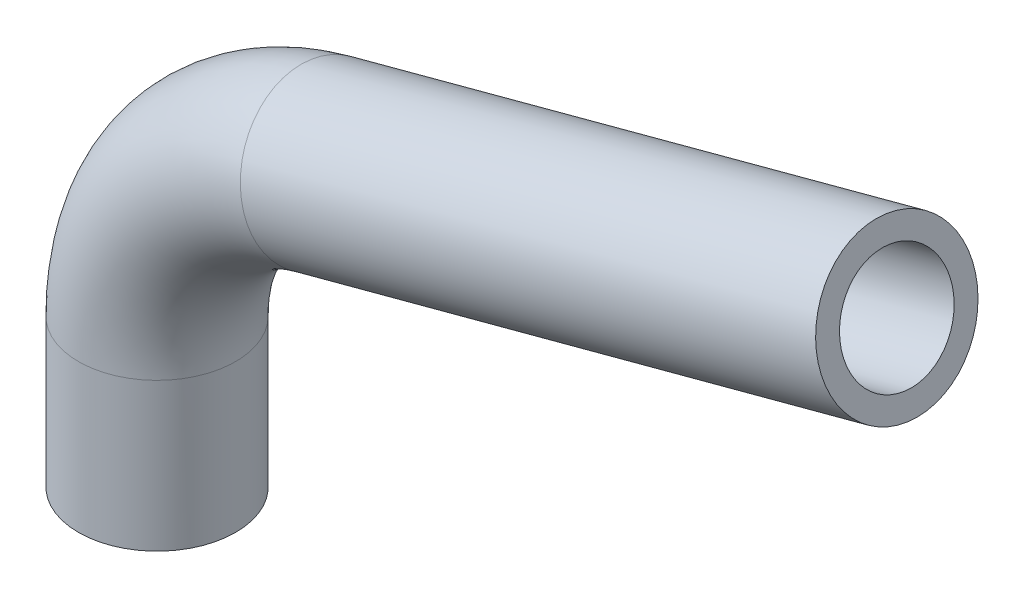
SolidWorks part; units mm, degrees
material "Silicon Rubber"
ref_plane "X-Y Datum" through (0, 0, 0) normal (0, 0, 1) x (1, 0, 0)
ref_plane "X-Z Datum" through (0, 0, 0) normal (0, 1, 0) x (1, 0, 0)
ref_plane "Y-Z Datum" through (0, 0, 0) normal (1, 0, 0) x (0, 0, -1)
sketch3d "3DSketch1"
  line L0 (0, 0, 0) -> (0, 25.4, 0)
  line L1 (28.239, 62.2018, 0) -> (127, 88.6647, 0)
  arc A1 (0, 25.4, 0) -> (28.239, 62.2018, 0) centre (38.1, 25.4, 0) cw
  point P4 (38.1, 25.4, -38.1)
  dimension "D2" = 75
  dimension "D1" = 38.1
  dimension "D3" = 127
  dimension "D4" = 25.4
sweep "Sweep1" add path "3DSketch1" circular profile diameter 26.9875 parameters "D3"=26.9875
sweep "Cut-Sweep1" cut path "3DSketch1<2>" circular profile diameter 19.05 parameters "D3"=19.05
sketch3d "3DSketch1<2>" same geometry as "3DSketch1"
